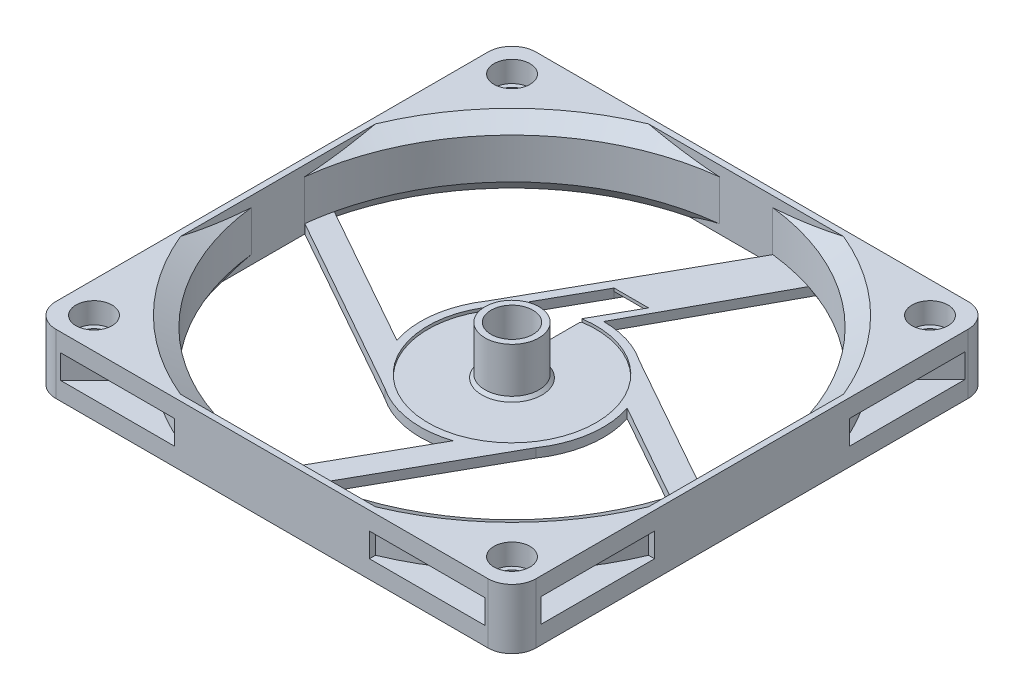
SolidWorks part; units mm, degrees
ref_plane "Front Plane" through (0, 0, 0) normal (0, 0, 1) x (1, 0, 0)
ref_plane "Top Plane" through (0, 0, 0) normal (0, 1, 0) x (1, 0, 0)
ref_plane "Right Plane" through (0, 0, 0) normal (1, 0, 0) x (0, 0, -1)
sketch "Sketch1" plane through (0, 0, 0) normal (0, 1, 0) x (1, 0, 0)
  line L1 (-36, 40) -> (36, 40)
  line L2 (-40, 36) -> (-40, -36)
  line L3 (-36, -40) -> (36, -40)
  line L4 (40, 36) -> (40, -36)
  circle A0 centre (0, 0) radius 39.25
  circle A1 centre (-34.825, 34.825) radius 2.25
  circle A2 centre (34.825, -34.825) radius 2.25
  arc A3 (-36, 40) -> (-40, 36) centre (-36, 36) ccw
  arc A4 (-40, -36) -> (-36, -40) centre (-36, -36) ccw
  arc A5 (36, -40) -> (40, -36) centre (36, -36) ccw
  arc A6 (36, 40) -> (40, 36) centre (36, 36) cw
  dimension "D5" = 4.5
  dimension "D6" = 4.5
  dimension "D9" = 4
  dimension "D10" = 4
  dimension "D11" = 78.5
  dimension "D1" = 40
  dimension "D2" = 40
  dimension "D3" = 40
  dimension "D4" = 40
  dimension "D7" = 49.25
  dimension "D8" = 49.25
extrude "Boss-Extrude1" add sketch "Sketch1" along normal blind 10
sketch "Sketch2" plane through (0, 10, 0) normal (0, 1, 0) x (1, 0, 0)
  circle A0 centre (-34.825, -34.825) radius 2.25
  circle A1 centre (34.825, 34.825) radius 2.25
extrude "Cut-Extrude1" cut sketch "Sketch2" against normal blind 10
sketch "Sketch3" plane through (0, 10, 0) normal (0, 1, 0) x (1, 0, 0)
  circle A0 centre (-34.825, -34.825) radius 3
extrude "Cut-Extrude2" cut sketch "Sketch3" against normal blind 3.5
sketch "Sketch4" plane through (0, 0, 0) normal (0, -1, 0) x (1, 0, 0)
  circle A0 centre (-34.825, 34.825) radius 3
extrude "Cut-Extrude3" cut sketch "Sketch4" against normal blind 2.5
pattern_linear "LPattern1" count 2 spacing 69.65 along (1, 0, 0) count 2 spacing 69.65 along (0, 0, -1) of "Cut-Extrude2", "Cut-Extrude3"
chamfer "Chamfer1" distance 3 angle 30 1 edges at (0, 10, 39.25) first distance on face at (34.825, 10, -31.825)
sketch "Sketch5" plane through (0, 10, 0) normal (0, 1, 0) x (1, 0, 0)
  line L0 (-40, 36) -> (-40, 13.6038) construction
  line L1 (-40, 24.8019) -> (-39, 24.8019)
  line L2 (-40, 24.8019) -> (-40, -19.1954)
  line L3 (-40, -19.1954) -> (-39, -19.1954)
  line L4 (-39, 24.8019) -> (-39, -19.1954)
  dimension "D1" = 1
extrude "Boss-Extrude3" add sketch "Sketch5" against normal up to surface (10 mm away) up to face at (34.825, 0, -37.825)
ref_axis "Axis1" through (0, 8.2679, 0) along (0, -1, 0)
pattern_circular "CirPattern1" count 4 every 90 about axis through (0, 8.2679, 0) along (0, -1, 0) of "Boss-Extrude3"
sketch "Sketch6" plane through (0, 0, 0) normal (0, -1, 0) x (1, 0, 0)
  line L2 (-39.0847, -4.524) -> (-8.5858, 12.5977)
  line L3 (-4.524, 39.0847) -> (12.5977, 8.5858)
  line L4 (-38.3696, -8.7098) -> (-14.5072, 4.6864)
  line L5 (-8.7098, 38.3696) -> (4.6864, 14.5072)
  line L6 (39.0847, 4.524) -> (8.5858, -12.5977)
  line L7 (38.3696, 8.7098) -> (14.5072, -4.6864)
  line L8 (4.524, -39.0847) -> (-12.5977, -8.5858)
  line L9 (0.0242, -15.2453) -> (12.0971, -37.4398)
  line L10 (8.7098, -38.3696) -> (-4.6864, -14.5072) [skipped]
  arc A0 (-8.5858, 12.5977) -> (4.6864, 14.5072) centre (0, 0) cw
  arc A1 (-39.0847, -4.524) -> (-38.3696, -8.7098) centre (0, 0) ccw
  arc A2 (4.524, -39.0847) -> (12.0971, -37.4398) centre (0, 0) ccw
  arc A4 (-8.7098, 38.3696) -> (-4.524, 39.0847) centre (0, 0) cw
  arc A5 (38.3696, 8.7098) -> (39.0847, 4.524) centre (0, 0) cw
  arc A6 (14.5072, -4.6864) -> (12.5977, 8.5858) centre (0, 0) ccw
  arc A7 (0.0242, -15.2453) -> (8.5858, -12.5977) centre (0, 0) ccw
  arc A8 (-14.5072, 4.6864) -> (-12.5977, -8.5858) centre (0, 0) ccw
  circle A9 centre (0, 0) radius 3.4
  dimension "D1" = 4
  dimension "D2" = 4
extrude "Boss-Extrude4" add sketch "Sketch6" against normal blind 1.5
sketch "Sketch7" plane through (0, 1.5, 0) normal (0, 1, 0) x (1, 0, 0)
  circle A0 centre (0, 0) radius 4.5
extrude "Boss-Extrude5" add sketch "Sketch7" along normal blind 7.5
sketch "Sketch8" plane through (0, 9, 0) normal (0, 1, 0) x (1, 0, 0)
  circle A0 centre (0, 0) radius 3.5
extrude "Cut-Extrude4" cut sketch "Sketch8" against normal blind 20
sketch "Sketch9" plane through (0, 1.5, 0) normal (0, 1, 0) x (1, 0, 0)
  line L0 (-3.9354, 20.9517) -> (-8.9879, 11.9517)
  line L1 (-8.9879, 11.9517) -> (-8.9879, 7.9517)
  line L2 (-8.9879, 7.9517) -> (-2.3394, 7.9517)
  line L3 (-2.3394, 7.9517) -> (-2.3394, 12.3498)
  line L4 (-2.3394, 12.3498) -> (-2.3394, 13.5809)
  line L5 (-2.3394, 13.5809) -> (1.7986, 20.9517)
  line L6 (1.7986, 20.9517) -> (-3.9354, 20.9517)
  line L8 (-12.5977, 8.5858) -> (4.4732, 38.9943) construction
  dimension "D1" = 1.5
  dimension "D2" = 5
  dimension "D3" = 4
  dimension "D4" = 9
extrude "Cut-Extrude5" cut sketch "Sketch9" against normal blind 5
sketch "Sketch10" plane through (0, 0, 0) normal (0, -1, 0) x (1, 0, 0)
  line L0 (-3.9354, -20.9517) -> (6.5309, -40)
  line L1 (36, -40) -> (-36, -40) construction
  line L2 (1.7986, -20.9517) -> (12.2649, -40)
  line L3 (12.2649, -40) -> (6.5309, -40)
  line L4 (-3.9354, -20.9517) -> (1.7986, -20.9517)
extrude "Cut-Extrude6" cut sketch "Sketch10" against normal blind 1
ref_plane "Plane1" through (0, 5, 0) normal (0, 1, 0) x (-1, 0, 0)
sketch "Sketch12" plane through (0, 5, 0) normal (0, 1, 0) x (-1, 0, 0)
  line L0 (32.5622, -37.0877) -> (27.5267, -32.0522)
  line L1 (32.5622, -37.0877) -> (35.4745, -40)
  line L2 (-36, -40) -> (36, -40) construction
  line L3 (35.4745, -40) -> (16.25, -40)
  line L4 (16.25, -40) -> (16.25, -39)
  line L5 (37.0751, -32.2667) -> (32.1825, -27.3742)
  line L6 (37.0751, -32.2667) -> (40, -35.1917)
  line L7 (40, -36) -> (40, 36) construction
  line L8 (39, -16.25) -> (40, -16.25)
  line L9 (40, -16.25) -> (40, -35.1917)
  line L10 (34.825, -34.825) -> (0, 0) construction
  arc A0 (16.25, -39) -> (27.5267, -32.0522) centre (0, 0) ccw
  arc A2 (16.25, -39) -> (39, -16.25) centre (0, 0) ccw construction
  arc A4 (32.1825, -27.3742) -> (39, -16.25) centre (0, 0) ccw
  dimension "D1" = 3.2
  dimension "D2" = 3.4
extrude "Cut-Extrude8" cut sketch "Sketch12" against normal blind 2 and the other way blind 2
pattern_circular "CirPattern2" count 4 every 90 about axis through (0, 8.2679, 0) along (0, -1, 0) of "Cut-Extrude8"
sketch "Sketch13" plane through (0, 1.5, 0) normal (0, 1, 0) x (1, 0, 0)
  circle A0 centre (0, 0) radius 14
  circle A1 centre (0, 0) radius 5
extrude "Cut-Extrude9" cut sketch "Sketch13" against normal blind 0.5
chamfer "Chamfer3" distance 0.5 angle 45 1 edges at (0, 1.5, 5)
chamfer "Chamfer5" distance 1.5 angle 30 1 edges at (30.3753, 0, -24.8576) first distance on face at (16.3533, 2.442, -31.2178)
chamfer "Chamfer6" distance 1.5 angle 30 1 edges at (-26.1926, 0, -29.232) first distance on face at (-31.5423, 2.442, -15.571)
chamfer "Chamfer7" distance 1.5 angle 30 1 edges at (-29.232, 0, 26.1926) first distance on face at (-15.571, 2.442, 31.5423)
chamfer "Chamfer8" distance 1.5 angle 30 1 edges at (26.1926, 0, 29.232) first distance on face at (31.5423, 2.442, 15.571)
